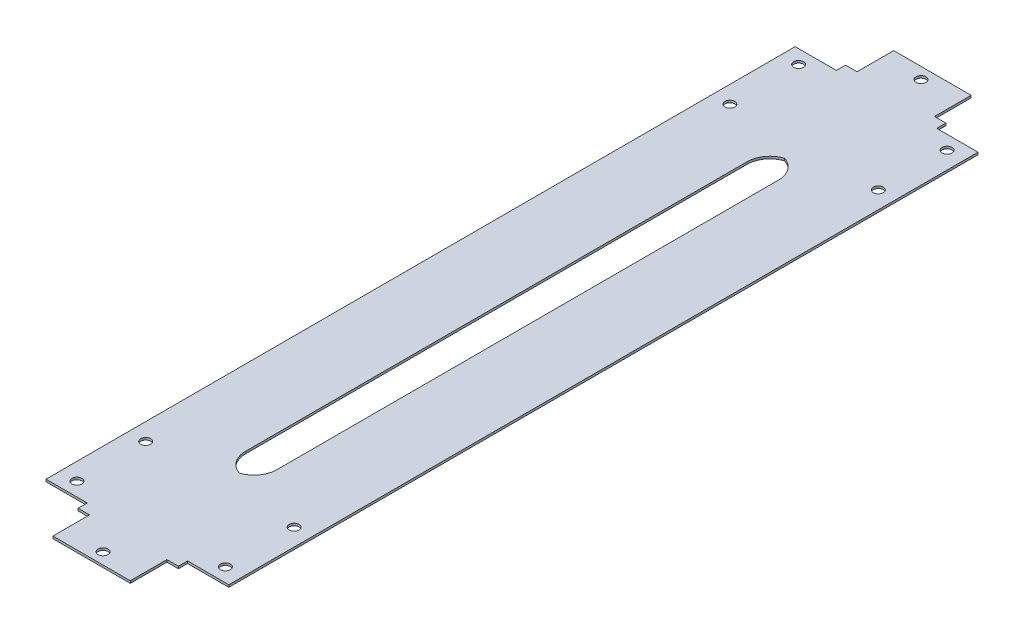
SolidWorks part; units mm, degrees
ref_plane "Front Plane" through (0, 0, 0) normal (0, 0, 1) x (1, 0, 0)
ref_plane "Top Plane" through (0, 0, 0) normal (0, 1, 0) x (1, 0, 0)
ref_plane "Right Plane" through (0, 0, 0) normal (1, 0, 0) x (0, 0, -1)
sketch "Sketch1" plane through (0, 0, 0) normal (0, 1, 0) x (1, 0, 0)
  line L0 (0, 0) -> (0, 163.5) construction
  line L1 (-39.9, -163.5) -> (-21.9, -163.5)
  line L3 (-21.9, 163.5) -> (-39.9, 163.5)
  line L4 (-39.9, 163.5) -> (-39.9, -163.5)
  line L16 (21.9, -163.5) -> (39.9, -163.5)
  line L17 (39.9, -163.5) -> (39.9, 163.5)
  line L25 (39.9, 163.5) -> (21.9, 163.5)
  line L26 (21.9, 163.5) -> (21.9, -163.5) construction
  line L27 (-6.9, 0) -> (0, 0) construction
  line L28 (-21.9, 163.5) -> (-21.9, 167.5)
  line L31 (-21.9, -163.5) -> (21.9, -163.5) construction
  line L32 (-21.9, 167.5) -> (-16.9, 167.5)
  line L33 (-16.9, 167.5) -> (-16.9, 183.5)
  line L35 (-21.9, 163.5) -> (21.9, 163.5) construction
  line L37 (-21.9, -163.5) -> (-21.9, 163.5) construction
  line L38 (0, 0) -> (6.9, 0) construction
  line L39 (-16.9, 183.5) -> (16.9, 183.5)
  line L40 (16.9, 183.5) -> (16.9, 167.5)
  line L41 (-6.9, 0) -> (-39.9, 0) construction
  line L42 (-6.9, 119.5) -> (6.9, 119.5)
  line L43 (-6.9, 119.5) -> (-6.9, -119.5)
  line L44 (-6.9, -119.5) -> (6.9, -119.5)
  line L45 (6.9, 119.5) -> (6.9, -119.5)
  line L46 (-6.9, 119.5) -> (6.9, -119.5) construction
  line L47 (-6.9, -119.5) -> (6.9, 119.5) construction
  line L48 (32.4, -127.5) -> (-32.4, -127.5) construction
  line L49 (32.4, -127.5) -> (32.4, 127.5) construction
  line L50 (32.4, 127.5) -> (-32.4, 127.5) construction
  line L51 (-32.4, -127.5) -> (-32.4, 127.5) construction
  line L52 (32.4, -127.5) -> (-32.4, 127.5) construction
  line L53 (32.4, 127.5) -> (-32.4, -127.5) construction
  line L54 (32.4, 157.5) -> (-32.4, 157.5) construction
  line L55 (32.4, 157.5) -> (32.4, -157.5) construction
  line L56 (32.4, -157.5) -> (-32.4, -157.5) construction
  line L57 (-32.4, 157.5) -> (-32.4, -157.5) construction
  line L58 (32.4, 157.5) -> (-32.4, -157.5) construction
  line L59 (32.4, -157.5) -> (-32.4, 157.5) construction
  line L60 (6.9, 0) -> (39.9, 0) construction
  line L61 (16.9, 167.5) -> (21.9, 167.5)
  line L62 (21.9, 167.5) -> (21.9, 163.5)
  line L63 (-16.9, 167.5) -> (16.9, 167.5) construction
  line L64 (0, 163.5) -> (0, 167.5) construction
  line L65 (-21.9, -163.5) -> (-21.9, -167.5)
  line L66 (-21.9, -167.5) -> (-16.9, -167.5)
  line L67 (-16.9, -167.5) -> (-16.9, -183.5)
  line L68 (-16.9, -183.5) -> (16.9, -183.5)
  line L69 (16.9, -183.5) -> (16.9, -167.5)
  line L70 (16.9, -167.5) -> (21.9, -167.5)
  line L71 (21.9, -167.5) -> (21.9, -163.5)
  line L72 (-16.9, -167.5) -> (16.9, -167.5) construction
  line L73 (0, -183.5) -> (0, -178.5) construction
  line L74 (0, 167.5) -> (0, 178.5) construction
  line L75 (0, 178.5) -> (0, 183.5) construction
  line L76 (0, -178.5) -> (0, -167.5) construction
  line L77 (0, -167.5) -> (0, -163.5) construction
  line L78 (0, -163.5) -> (0, 0) construction
  circle A2 centre (-32.4, 127.5) radius 2.15
  circle A3 centre (32.4, 127.5) radius 2.15
  circle A4 centre (-32.4, -127.5) radius 2.15
  circle A5 centre (32.4, -127.5) radius 2.15
  circle A6 centre (-32.4, -157.5) radius 2.15
  circle A7 centre (32.4, -157.5) radius 2.15
  circle A8 centre (32.4, 157.5) radius 2.15
  circle A9 centre (-32.4, 157.5) radius 2.15
  circle A10 centre (0, 178.5) radius 2.15
  circle A11 centre (0, -178.5) radius 2.15
  point P0 (0, 0)
  point P37 (0, 0)
  point P40 (0, 0)
  dimension "D12" = 4.3
  dimension "D5" = 30
  dimension "D15" = 64.8
  dimension "D3" = 10.5
  dimension "D14" = 10.5
  dimension "D4" = 18
  dimension "D16" = 18
  dimension "D18" = 4
  dimension "D11" = 38
  dimension "D7" = 10
  dimension "D6" = 21
  dimension "D9" = 4
  dimension "D19" = 33.8
  dimension "D20" = 5
  dimension "D8" = 43.8
  dimension "D13" = 315
  dimension "D17" = 335
  dimension "D21" = 327
  dimension "D10" = 15
extrude "Boss-Extrude1" add sketch "Sketch1" along normal blind 1
fillet "Fillet2" radius 10 4 edges at (6.9, 0.5, -119.5) (-6.9, 0.5, -119.5) (6.9, 0.5, 119.5) (-6.9, 0.5, 119.5)
equation "\"skin_sheetmetal_thickness\"= 0.80"
equation "\"base_width_skin_spacer\" = \"base_width_skin_target_width\" - 4 * \"skin_sheetmetal_thickness\" - 2 * \"base_width_skin_target_bend_radius\""
equation "\"base_width_skin_inner\" = \"base_width_skin_spacer\" + 2 * \"skin_sheetmetal_thickness\""
equation "\"base_width_skin_outer\" = \"base_width_skin_inner\" + 2 * \"skin_sheetmetal_thickness\""
equation "\"bend_cut_width\"= 3"
equation "\"bend_cut_length\"= 3"
equation "\"bend_offset_inner\"= 12.5"
equation "\"bend_offset_outer\" = \"bend_offset_inner\" + \"skin_sheetmetal_thickness\""
equation "\"border_offset_ends\"= 20"
equation "\"border_offset_sides\"= 10"
equation "\"border_offset_flange_horiz\"= 10"
equation "\"rivet_size\"= 4.3"
equation "\"rivet_offset_ends\"= \"rivet_spacing_horiz\"/2 - \"border_offset_ends\""
equation "\"rivet_spacing_horiz\"= 200"
equation "\"rivet_spacing_vert\"= 30"
equation "\"rivet_spacing_offset_right\"= 40"
equation "\"base_length\"= 200"
equation "\"D8@Sketch1\"=\"base_width_skin_spacer\""
equation "\"D19@Sketch1\"=\"base_width_skin_spacer\" - 10"
equation "\"D5@Sketch1\"=\"rivet_spacing_vert\""
equation "\"base_width_skin_spacer_length\" = 315"
equation "\"D13@Sketch1\"=\"base_width_skin_spacer_length\""
equation "\"bend_offset_spacer_tab\"= 21.0"
equation "\"D6@Sketch1\"=\"bend_offset_spacer_tab\""
equation "\"base_width_skin_target_width\" = 50"
equation "\"base_width_skin_target_bend_radius\" = 1.5"
